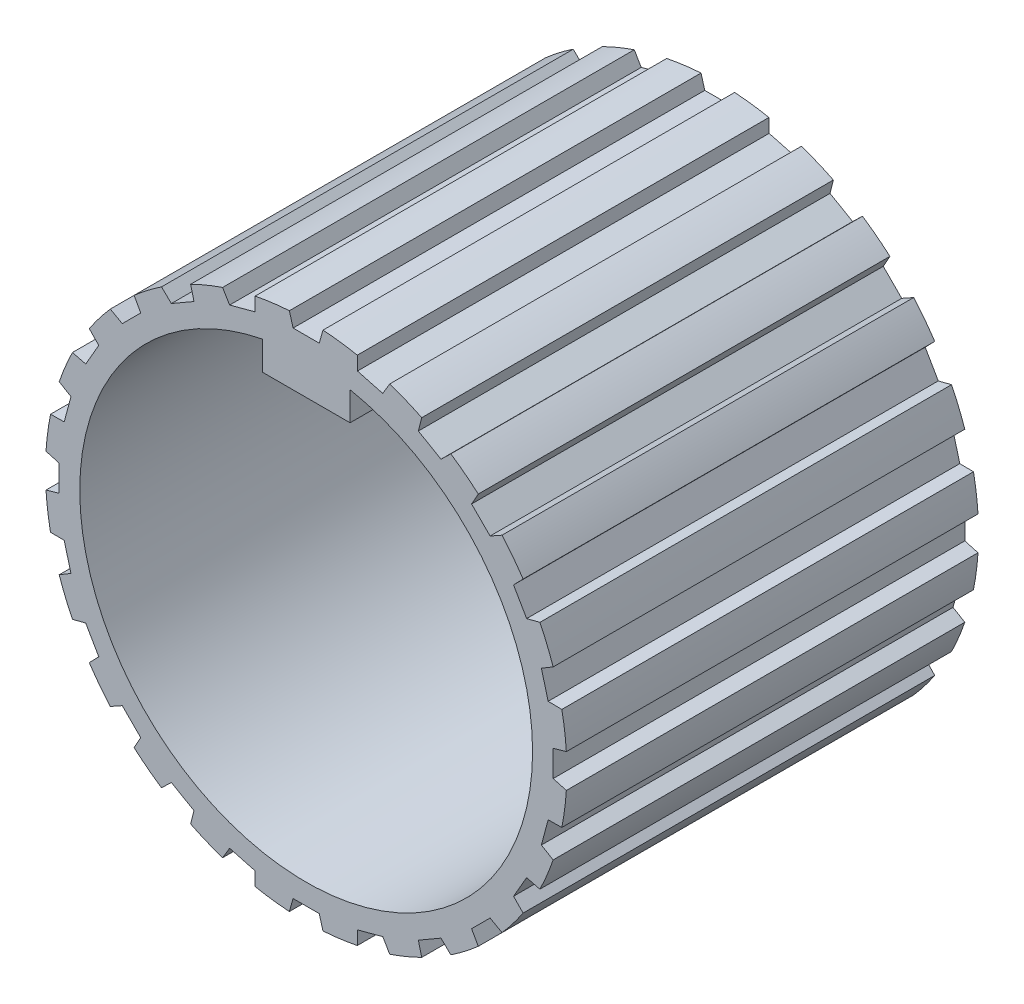
SolidWorks part; units mm, degrees
ref_plane "Front Plane" through (0, 0, 0) normal (0, 0, 1) x (1, 0, 0)
ref_plane "Top Plane" through (0, 0, 0) normal (0, 1, 0) x (1, 0, 0)
ref_plane "Right Plane" through (0, 0, 0) normal (1, 0, 0) x (0, 0, -1)
sketch "Sketch2" plane through (0, 0, 0) normal (0, 0, 1) x (1, 0, 0)
  line L0 (0, 0) -> (0, 7.05) construction
  line L1 (0, 9.5006) -> (0, 9.0006) construction
  line L2 (1.6, 7.05) -> (-1.6, 7.05)
  line L3 (-1.6, 7.05) -> (-1.6, 8.0934)
  line L4 (1.6, 7.05) -> (1.6, 8.0934)
  line L5 (0.4726, 9.0006) -> (-0.4726, 9.0006)
  line L6 (-0.4726, 9.0006) -> (-0.4726, 9.4882)
  line L7 (0.4726, 9.0006) -> (0.4726, 9.4882)
  arc A0 (-1.6, 8.0934) -> (1.6, 8.0934) centre (0, 0) ccw
  arc A1 (-0.4726, 9.4882) -> (0.4726, 9.4882) centre (0, 0) ccw
  dimension "D1" = 16.5
  dimension "D2" = 19
  dimension "D3" = 1.6
  dimension "D4" = 0.5
extrude "Boss-Extrude1" add sketch "Sketch2" along normal mid plane 15
chamfer "Chamfer1" distance 0.5 angle 15 1 edges at (-0.4726, 9.4882, 0) first distance on face at (-0.4726, 9.2444, 0)
chamfer "Chamfer2" distance 0.5 angle 15 1 edges at (0.4726, 9.4882, 0) first distance on face at (0.4726, 9.2444, 0)
pattern_circular "CirPattern2" count 24 over 360 about axis through (0, 0, 7.5) along (0, 0, -1) of face at (0, 9.0006, 0) of face at (-0.5442, 9.2404, 0) of face at (0.5442, 9.2404, 0)
